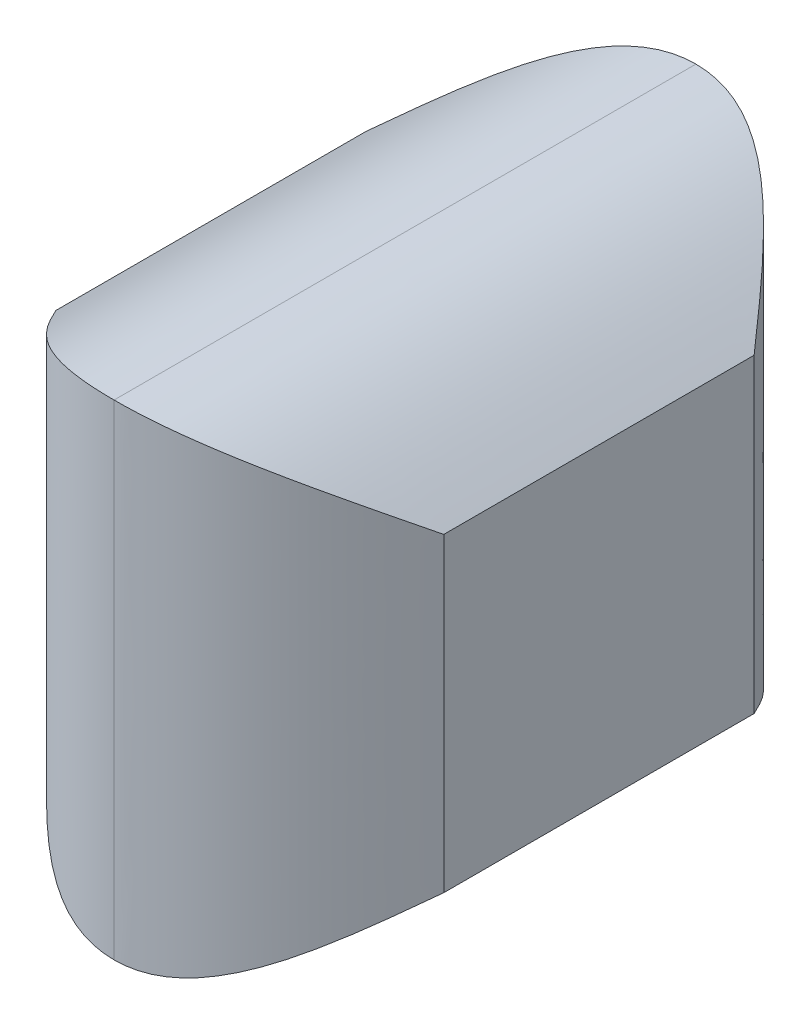
SolidWorks part; units mm, degrees
ref_plane "Front Plane" through (0, 0, 0) normal (0, 0, 1) x (1, 0, 0)
ref_plane "Top Plane" through (0, 0, 0) normal (0, 1, 0) x (1, 0, 0)
ref_plane "Right Plane" through (0, 0, 0) normal (1, 0, 0) x (0, 0, -1)
sketch "Sketch1" plane through (300, 0, 0) normal (1, 0, 0) x (0, 0, -1)
  line L1 (150, 0) -> (150, 125) construction
  line L2 (150, 125) -> (0, 125) construction
  line L8 (35, 102.5) -> (35, 22.5)
  line L9 (35, 22.5) -> (115, 22.5)
  line L10 (115, 22.5) -> (115, 102.5)
  line L11 (115, 102.5) -> (35, 102.5)
  dimension "D1" = 80
  dimension "D2" = 80
  dimension "D3" = 35
  dimension "D4" = 22.5
ref_plane "Plane1" through (350, 0, 0) normal (1, 0, 0) x (0, 0, -1)
sketch "Sketch2" plane through (350, 0, 0) normal (1, 0, 0) x (0, 0, -1)
  line L4 (0, 125) -> (0, 0) construction
  line L5 (0, 0) -> (150, 0) construction
  line L6 (150, 125) -> (0, 125) construction
  line L7 (150, 0) -> (150, 125) construction
  line L8 (0, 125) -> (0, 0)
  line L9 (0, 0) -> (150, 0)
  line L10 (150, 0) -> (150, 125)
  line L11 (150, 125) -> (0, 125)
loft "Loft1" add profiles "Sketch1", "Sketch2" end constraint normal to profile end tangent length 1 connector at (300, 102.5, -115) connector at (350, 125, -150)
mirror "Mirror1" about plane through (350, 0, 0) normal (1, 0, 0) of "Loft1"
